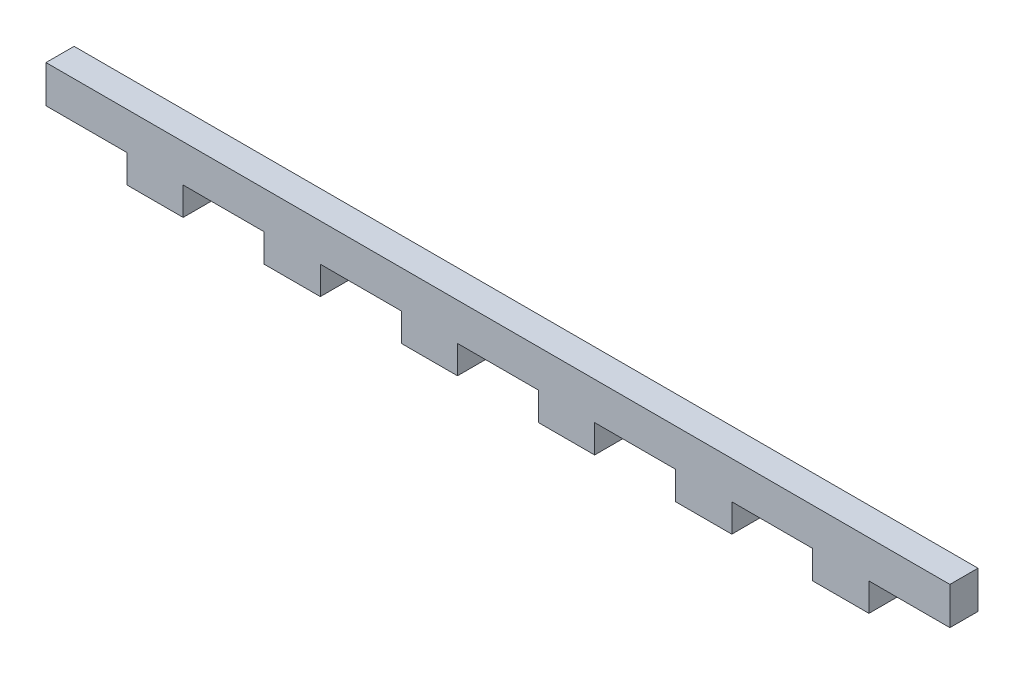
SolidWorks part; units mm, degrees
ref_plane "Front Plane" through (0, 0, 0) normal (0, 0, 1) x (1, 0, 0)
ref_plane "Top Plane" through (0, 0, 0) normal (0, 1, 0) x (1, 0, 0)
ref_plane "Right Plane" through (0, 0, 0) normal (1, 0, 0) x (0, 0, -1)
sketch "Sketch2" plane through (0, 0, 0) normal (0, 1, 0) x (1, 0, 0)
  line L0 (0, 0) -> (0, 6) construction
  dimension "D1" = 6
sketch "Sketch1" plane through (0, 0, 0) normal (0, 0, 1) x (1, 0, 0)
  line L1 (-96.5, -7) -> (96.5, -7)
  line L2 (-96.5, -7) -> (-96.5, 7)
  line L3 (-96.5, 7) -> (96.5, 7)
  line L4 (96.5, -7) -> (96.5, 7)
  line L5 (-96.5, -7) -> (96.5, 7) construction
  line L6 (-96.5, 7) -> (96.5, -7) construction
  point P0 (0, 0)
  dimension "D1" = 14
  dimension "D2" = 193
extrude "Boss-Extrude1" add sketch "Sketch1" against normal up to vertex (6 mm away) contours L2 L3 L4 L1 up to point (0, 0, -6)
sketch "Sketch3" plane through (0, 0, 0) normal (0, 0, 1) x (1, 0, 0)
  line L0 (-96.5, -7) -> (-96.5, 7) construction
  line L1 (-96.5, -1) -> (-79.2143, -1)
  line L2 (-96.5, -1) -> (-96.5, -7)
  line L3 (-96.5, -7) -> (-79.2143, -7)
  line L4 (-79.2143, -1) -> (-79.2143, -7)
  line L5 (-96.5, -7) -> (96.5, -7) construction
  line L6 (0, -1) -> (0, 0) construction
  line L7 (-79.2143, -1) -> (-67.2143, -1)
  line L8 (-79.2143, -1) -> (-79.2143, -7)
  line L9 (-79.2143, -7) -> (-67.2143, -7)
  line L10 (-67.2143, -1) -> (-67.2143, -7)
  line L11 (-67.2143, -1) -> (-49.9286, -1)
  line L12 (-67.2143, -1) -> (-67.2143, -7)
  line L13 (-67.2143, -7) -> (-49.9286, -7)
  line L14 (-49.9286, -1) -> (-49.9286, -7)
  line L15 (-49.9286, -1) -> (-37.9286, -1)
  line L16 (-49.9286, -1) -> (-49.9286, -7)
  line L17 (-49.9286, -7) -> (-37.9286, -7)
  line L18 (-37.9286, -1) -> (-37.9286, -7)
  line L19 (-37.9286, -1) -> (-20.6429, -1)
  line L20 (-37.9286, -1) -> (-37.9286, -7)
  line L21 (-37.9286, -7) -> (-20.6429, -7)
  line L22 (-20.6429, -1) -> (-20.6429, -7)
  line L23 (-20.6429, -1) -> (-8.6429, -1)
  line L24 (-20.6429, -1) -> (-20.6429, -7)
  line L25 (-20.6429, -7) -> (-8.6429, -7)
  line L26 (-8.6429, -1) -> (-8.6429, -7)
  line L27 (8.6429, -1) -> (-8.6429, -1)
  line L28 (0, -1) -> (0, -7)
  point P30 (0, -1)
  line M27 (-96.5, -7) -> (96.5, -7)
  line M30 (-96.5, 7) -> (-96.5, -7)
  dimension "D1" = 12
  dimension "D2" = 6
extrude "Cut-Extrude1" cut sketch "Sketch3" against normal through all contours L4 L1 M30 M27 | L14 L11 L10 M27 | L22 L19 L18 M27 | L28 L27 L26 M27 region at (-87.8571, -4, 0) region at (-58.5714, -4, 0) region at (-29.2857, -4, 0) region at (-4.3214, -4, 0)
mirror "Mirror1" about plane through (0, 0, 0) normal (1, 0, 0) of "Cut-Extrude1"
equation "\"t_wood\"= 6' Thickness of the wood"
equation "\"t_glass\"= 2.5'Thickness of glass panels"
equation "\"w_glass\"= 181"
equation "\"h_glass\"= 151"
equation "\"h_food_internal\" = 60"
equation "\"entry_height\"= 20"
equation "\"entry diameter\"= 8"
equation "\"glass_bottom_overlap\"= 8"
equation "\"default_finger_size\"= 12"
equation "\"brood_depth\"= 42"
equation "\"outer_box_depth\" = \"brood_depth\" + ( 2 * \"t_glass\" ) + ( 2 * \"t_wood\" )"
equation "\"outer_box_width\"= \"w_glass\" + ( 2 * \"t_wood\" )"
equation "\"food_top_clearance\"= 10"
equation "\"outer_box_height\"= \"t_wood\" + \"h_glass\" + \"t_wood\" + \"h_food_internal\" + \"food_top_clearance\" + \"t_wood\""
equation "\"food_internal_depth\"= \"brood_depth\" + \"t_glass\" + \"t_glass\" - \"t_wood\" - \"t_wood\""
equation "\"food_channel_clearance_width\"= 14"
equation "\"bar_top_play\"= 0.5"
equation "\"bar_entry_angle\"= 10"
equation "\"bar_width\"= 20"
equation "\"entry_disk_play\"= 0.3"
equation "\"D1@Sketch2\"=\"t_wood\""
equation "\"D1@Sketch1\"=\"t_wood\"+\"glass_bottom_overlap\""
equation "\"D2@Sketch1\"=\"outer_box_width\""
equation "\"D1@Sketch3\"=\"default_finger_size\""
